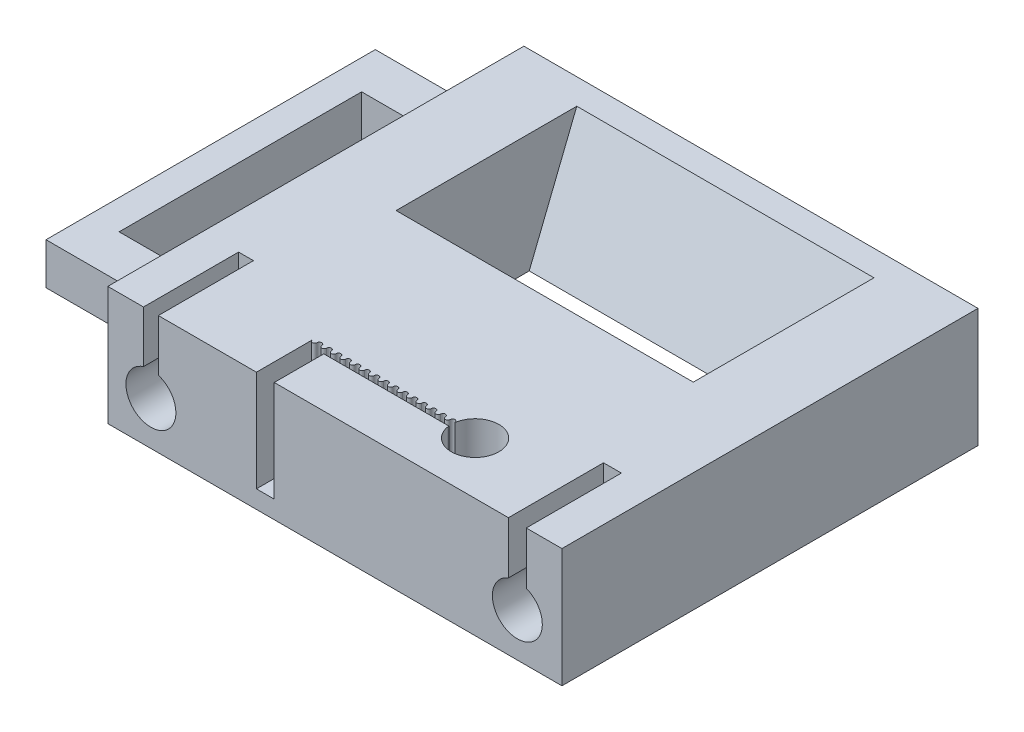
SolidWorks part; units mm, degrees
ref_plane "Front Plane" through (0, 0, 0) normal (0, 0, 1) x (1, 0, 0)
ref_plane "Top Plane" through (0, 0, 0) normal (0, 1, 0) x (1, 0, 0)
ref_plane "Right Plane" through (0, 0, 0) normal (1, 0, 0) x (0, 0, -1)
sketch "Sketch1" plane through (0, 0, 0) normal (0, 1, 0) x (1, 0, 0)
  line L0 (0, 0) -> (76.4, 0)
  line L1 (-11, 0) -> (11, 0) construction
  line L2 (76.4, 0) -> (76.4, 16)
  line L3 (76.4, 16) -> (76.4, 70)
  line L4 (76.4, 70) -> (0, 70)
  line L5 (0, -11) -> (0, 11) construction
  line L6 (0, 70) -> (0, 0)
  dimension "D1" = 16
  dimension "D2" = 76.4
  dimension "D3" = 54
  dimension "D4" = 70
extrude "Boss-Extrude1" add sketch "Sketch1" along normal blind 20
sketch "Sketch2" plane through (0, 20, 0) normal (0, 1, 0) x (1, 0, 0)
  line L0 (0, 0) -> (5.9, 0)
  line L1 (0, 0) -> (76.4, 0) construction
  line L2 (5.9, 0) -> (5.9, 16)
  line L3 (5.9, 16) -> (0, 16)
  line L4 (0, 16) -> (0, 0)
  line L5 (5.9, 16) -> (8.7, 16)
  line L6 (8.7, 16) -> (8.7, 0)
  line L7 (8.7, 16) -> (67.7, 16)
  line L8 (67.7, 16) -> (70.5, 16)
  line L9 (67.7, 16) -> (67.7, 0)
  line L10 (70.5, 16) -> (76.4, 16)
  line L12 (76.4, 0) -> (76.4, 70) construction
  line L13 (76.4, 16) -> (76.4, 0)
  line L14 (76.4, 0) -> (5.9, 0)
  line L15 (0, 0) -> (25, 0)
  line L16 (25, 0) -> (25, 9.4)
  line L17 (25, 9.4) -> (28, 9.4)
  line L19 (28, 0) -> (25, 0)
  line L20 (28, 9.4) -> (49, 9.4)
  line L24 (28, 8.18) -> (49, 8.18)
  line L26 (28, 8.18) -> (28, 0)
  line L27 (49, 9.4) -> (49.0468, 9.4)
  line L28 (49, 8.18) -> (49.0468, 8.18)
  line L29 (25, 0) -> (28, 0)
  circle A1 centre (53, 8.79) radius 4
  dimension "D1" = 16
  dimension "D2" = 2.8
  dimension "D3" = 5.9
  dimension "D4" = 2.8
  dimension "D5" = 59
  dimension "D6" = 5.9
  dimension "D7" = 25
  dimension "D8" = 9.4
  dimension "D9" = 1.22
extrude "Cut-Extrude1" cut sketch "Sketch2" against normal blind 17 contours A1 L27 L20 L17 L16 L14 L26 L24 L28 | A1 region at (25.2582, 20, -4.7) region at (53, 20, -8.79)
sketch "Sketch4" plane through (0, 20, 0) normal (0, 1, 0) x (1, 0, 0)
  line L0 (25, 9.4) -> (25.8, 9.4)
  line L1 (25, 9.4) -> (25.4, 9.4)
  line L3 (25, 9.4) -> (49.0468, 9.4) construction
  line L4 (25, 0) -> (25, 9.4) construction
  line L5 (25, 0.2261) -> (25.9, 0.2261)
  line L6 (26.6, 9.4) -> (25.8, 9.4)
  arc A0 (25, 9.4) -> (25.8, 9.4) centre (25.4, 9.4) ccw
  arc A1 (25, 0.2261) -> (25.9, 0.2261) centre (25.45, 0.2261) ccw
  arc A2 (26.6, 9.4) -> (25.8, 9.4) centre (26.2, 9.4) ccw
  point P9 (25.4, 9.4)
  line M10 (25, 9.4) -> (49.0468, 9.4)
  dimension "D1" = 0.8
  dimension "D2" = 0.4
  dimension "D3" = 0.4
  dimension "D4" = 0
  dimension "D5" = 0
  dimension "D6" = 0
extrude "Boss-Extrude4" add sketch "Sketch4" against normal blind 17 contours A0 L0 M10 region at (25.4, 20, -9.2302)
pattern_linear "LPattern14" count 15 spacing 1.6 along (1, 0, 0) of "Boss-Extrude4"
sketch "Sketch8" plane through (0, 20, 0) normal (0, 1, 0) x (1, 0, 0)
  line L0 (25.8, 9.4) -> (26.6, 9.4)
  arc A0 (26.6, 9.4) -> (27.4, 9.4) centre (27, 9.4) ccw construction
  arc A1 (26.6, 9.4) -> (27.4, 9.4) centre (27, 9.4) ccw construction
  arc A2 (26.6, 9.4) -> (25.8, 9.4) centre (26.2, 9.4) ccw
extrude "Cut-Extrude4" cut sketch "Sketch8" against normal blind 17
pattern_linear "LPattern15" count 15 spacing 1.6 along (1, 0, 0) of "Cut-Extrude4"
sketch "Sketch9" plane through (0, 20, 0) normal (0, 1, 0) x (1, 0, 0)
  line L0 (28, 8.18) -> (28, 8.34)
  line L1 (28, 8.34) -> (48.9392, 8.34)
  line L2 (49.0468, 8.18) -> (49.0468, 8.34)
  line L3 (49.0468, 8.34) -> (48.9392, 8.34)
  line L4 (28, 8.18) -> (49.0468, 8.18)
extrude "Boss-Extrude5" add sketch "Sketch9" against normal blind 17
sketch "Sketch10" plane through (0, 20, 0) normal (0, 1, 0) x (1, 0, 0)
  line L0 (6, 16) -> (8.5, 16)
  line L1 (0, 0) -> (25, 0) construction
  line L3 (6, 0) -> (6, 16)
  line L4 (8.5, 16) -> (8.5, 0)
  line L5 (8.5, 0) -> (6, 0)
  line L7 (28, 0) -> (76.4, 0) construction
  line L8 (70.4, 0) -> (70.4, 16)
  line L9 (70.4, 16) -> (67.4, 16)
  line L10 (67.4, 16) -> (67.4, 0)
  line L11 (67.4, 0) -> (70.4, 0)
extrude "Cut-Extrude5" cut sketch "Sketch10" against normal blind 8.5
sketch "Sketch11" plane through (0, 0, 0) normal (0, 0, 1) x (1, 0, 0)
  line L0 (7.25, 11.5) -> (7.25, 7.3)
  line L1 (8.5, 11.5) -> (6, 11.5) construction
  line L2 (6, 11.5) -> (6, 11.3097)
  line L3 (8.5, 11.5) -> (8.5, 11.3097)
  circle A0 centre (7.25, 7.3) radius 4.2
  line M2 (8.5, 11.5) -> (6, 11.5)
extrude "Cut-Extrude7" cut sketch "Sketch11" against normal blind 16 contours A0 L2 M2 | A0 L3 M2 region at (6.3111, 11.4431, 0) region at (8.1889, 11.4431, 0)
extrude "Cut-Extrude8" cut sketch "Sketch11<4>" against normal blind 16 contours A0 region at (4.8314, 4.0126, 0)
sketch "Sketch11<4>" plane through (0, 0, 0) normal (0, 0, 1) x (1, 0, 0) same geometry as "Sketch11"
sketch "Sketch12" plane through (0, 0, 0) normal (0, 0, 1) x (1, 0, 0)
  line L0 (67.4, 11.5) -> (67.4, 11.223)
  line L2 (70.4, 11.5) -> (70.4, 11.223)
  circle A0 centre (68.9, 7.3) radius 4.2
  line M11 (70.4, 11.5) -> (67.4, 11.5)
extrude "Cut-Extrude9" cut sketch "Sketch12" against normal blind 16 contours A0 L0 M11 | A0 L2 M11 region at (67.7725, 11.4174, 0) region at (70.0275, 11.4174, 0)
extrude "Cut-Extrude10" cut sketch "Sketch12<3>" against normal blind 16 contours A0 region at (68.9, 7.3, 0)
sketch "Sketch12<3>" plane through (0, 0, 0) normal (0, 0, 1) x (1, 0, 0) same geometry as "Sketch12"
sketch "Sketch19" plane through (0, 20, 0) normal (0, 1, 0) x (1, 0, 0)
  line L0 (0, 70) -> (0, 14.6)
  line L1 (0, 70) -> (0, 0) construction
  line L3 (-25, 14.6) -> (-25, 70)
  line L4 (0, 70) -> (-25, 70)
  line L5 (-25, 14.6) -> (0, 14.6)
  line L6 (-25, 70) -> (-25, 62.7)
  line L7 (-25, 14.6) -> (-25, 21.9)
  line L8 (-25, 62.7) -> (0, 62.7)
  line L9 (0, 62.7) -> (0, 70)
  line L10 (-25, 21.9) -> (0, 21.9)
  line L11 (0, 21.9) -> (0, 14.6)
  line L12 (-25, 21.9) -> (-20, 21.9)
  line L13 (-20, 21.9) -> (-20, 62.7)
  line M51 (0, 70) -> (0, 0)
  dimension "D1" = 55.4
  dimension "D2" = 25
  dimension "D3" = 7.3
  dimension "D4" = 7.3
  dimension "D5" = 40.8
  dimension "D6" = 5
extrude "Boss-Extrude8" add sketch "Sketch19" against normal blind 20 contours L3 L8 L4 M51 | L10 L13 L8 L3 | L10 L3 L5 M51 region at (-12.5, 20, -66.35) region at (-12.5, 20, -18.25) region at (-22.5, 20, -42.3)
sketch "Sketch22" plane through (0, 20, 0) normal (0, 1, 0) x (1, 0, 0)
  line L0 (0, 62.7) -> (-20, 62.7)
  line L1 (-20, 62.7) -> (-20, 21.9)
  line L2 (-20, 21.9) -> (0, 21.9)
  line L3 (0, 21.9) -> (0, 62.7)
  line L4 (0, 62.7) -> (0, 70)
  line L5 (76.4, 70) -> (-25, 70) construction
  line L6 (0, 70) -> (-25, 70)
  line L7 (-25, 70) -> (-25, 14.6)
  line L8 (-25, 14.6) -> (0, 14.6)
  line L9 (0, 14.6) -> (0, 21.9)
extrude "Cut-Extrude11" cut sketch "Sketch22" against normal blind 6 contours L8 L9 L2 L1 L0 L4 L6 L7 region at (-10, 20, -63.3078)
sketch "Sketch23" plane through (0, 20, 0) normal (0, 1, 0) x (1, 0, 0)
  line L0 (0, 70) -> (0, 65.7)
  line L1 (0, 70) -> (0, 0) construction
  line L2 (0, 65.7) -> (0, 52.5)
  line L3 (0, 52.5) -> (76.4, 52.5)
  line L4 (76.4, 0) -> (76.4, 70) construction
  line L5 (0, 65.7) -> (0, 57.2)
  line L6 (0, 65.7) -> (0, 61.7)
  line L7 (0, 61.7) -> (13.2, 61.7)
  line L8 (13.2, 61.7) -> (63.2, 61.7)
  line L9 (63.2, 61.7) -> (76.4, 61.7)
  line L10 (0, 52.5) -> (0, 35.3)
  line L11 (0, 35.3) -> (13.2, 35.3)
  line L12 (13.2, 35.3) -> (63.2, 35.3)
  line L13 (63.2, 35.3) -> (76.4, 35.3)
  line L14 (13.2, 61.7) -> (13.2, 52.5)
  line L15 (13.2, 52.5) -> (13.2, 35.3)
  line L16 (63.2, 35.3) -> (63.2, 52.5)
  line L17 (63.2, 52.5) -> (63.2, 61.7)
  line L18 (0, 65.7) -> (76.4, 65.7)
  line L19 (13.2, 61.7) -> (13.2, 65.7)
  line L20 (63.2, 61.7) -> (63.2, 65.7)
  dimension "D1" = 4.3
  dimension "D2" = 17.5
  dimension "D3" = 13.2
  dimension "D4" = 8.5
  dimension "D5" = 4
  dimension "D6" = 76.4
  dimension "D7" = 30.4
extrude "Cut-Extrude12" cut sketch "Sketch23" against normal through all contours L8 L20 L18 L19 | L3 L17 L8 L14 | L12 L16 L3 L15 region at (38.2, 20, -63.7) region at (38.2, 20, -57.1) region at (38.2, 20, -43.9)
sketch "Sketch28" plane through (-25, 0, 0) normal (-1, 0, 0) x (0, 0, 1)
  line L0 (-70, 0) -> (-70, 14) construction
  line L1 (-70, 14) -> (-70, 7)
  line L2 (-70, 7) -> (-14.6, 7)
  line L3 (-14.6, 0) -> (-14.6, 14) construction
  line L4 (-14.6, 7) -> (-14.6, 14)
  line L5 (-14.6, 14) -> (-70, 14)
extrude "Cut-Extrude15" cut sketch "Sketch28" against normal up to surface (25 mm away) up to face at (0, 9.6, -33.84)
sketch "Sketch29" plane through (63.2, 0, 0) normal (-1, 0, 0) x (0, 0, 1)
  line L0 (-65.7, 0) -> (-57.7, 0)
  line L1 (-35.3, 0) -> (-65.7, 0) construction
  line L2 (-65.7, 0) -> (-65.7, 20)
  line L3 (-65.7, 20) -> (-57.7, 0)
  line L4 (-35.3, 0) -> (-45.3, 0)
  line L5 (-45.3, 0) -> (-35.3, 20)
  line L6 (-35.3, 20) -> (-35.3, 0)
extrude "Boss-Extrude10" add sketch "Sketch29" along normal up to next
